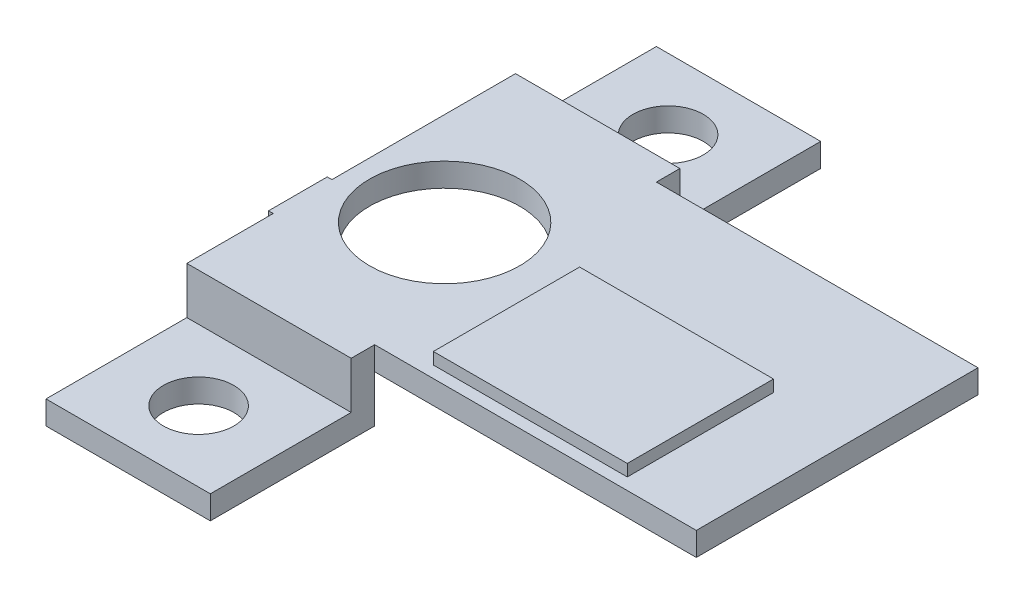
SolidWorks part; units mm, degrees
ref_plane "前视基准面" through (0, 0, 0) normal (0, 0, 1) x (1, 0, 0)
ref_plane "上视基准面" through (0, 0, 0) normal (0, 1, 0) x (1, 0, 0)
ref_plane "右视基准面" through (0, 0, 0) normal (1, 0, 0) x (0, 0, -1)
sketch "草图2" plane through (0, 0, 0) normal (0, 1, 0) x (1, 0, 0)
  line L1 (-8.9775, 5.0216) -> (11.7225, 5.0216)
  line L2 (-8.9775, 5.0216) -> (-8.9775, -6.9784)
  line L3 (-8.9775, -6.9784) -> (11.7225, -6.9784)
  line L4 (11.7225, 5.0216) -> (11.7225, -6.9784)
  line L5 (0.5225, -0.7484) -> (7.7825, -0.7484)
  line L6 (0.5225, -0.7484) -> (0.5225, -5.9784)
  line L7 (0.5225, -5.9784) -> (7.7825, -5.9784)
  line L8 (7.7825, -0.7484) -> (7.7825, -5.9784)
  circle A0 centre (-4.9975, -0.9784) radius 3.2
  dimension "D7" = 6.4
  dimension "D1" = 20.7
  dimension "D2" = 12
  dimension "D3" = 1
  dimension "D4" = 9.5
  dimension "D5" = 5.23
  dimension "D6" = 7.26
  dimension "D8" = 3.98
  dimension "D9" = 6
extrude "凸台-拉伸1" add sketch "草图2" along normal blind 1
sketch "草图3" plane through (0, 1, 0) normal (0, 1, 0) x (1, 0, 0)
  line L0 (7.7825, -5.9784) -> (7.7825, -0.7484) construction
  line L1 (0.0225, -0.2484) -> (8.2825, -0.2484)
  line L2 (0.0225, -0.2484) -> (0.0225, -6.4784)
  line L3 (0.0225, -6.4784) -> (8.2825, -6.4784)
  line L4 (8.2825, -0.2484) -> (8.2825, -6.4784)
  line L5 (7.7825, -0.7484) -> (0.5225, -0.7484) construction
  line L6 (0.5225, -0.7484) -> (0.5225, -5.9784) construction
  line L7 (0.5225, -5.9784) -> (7.7825, -5.9784) construction
  dimension "D1" = 0.5
  dimension "D2" = 0.5
  dimension "D3" = 0.5
  dimension "D4" = 0.5
extrude "凸台-拉伸2" add sketch "草图3" along normal blind 0.5
sketch "草图4" plane through (-8.9775, 0, 0) normal (-1, 0, 0) x (0, 0, 1)
  line L0 (-5.0216, 1) -> (6.9784, 1) construction
  line L1 (1.7984, 1) -> (4.2984, 1)
  line L2 (1.7984, 1) -> (1.7984, 0)
  line L3 (1.7984, 0) -> (4.2984, 0)
  line L4 (4.2984, 1) -> (4.2984, 0)
  line L5 (-5.0216, 0) -> (6.9784, 0) construction
  line L6 (6.9784, 1) -> (6.9784, 0) construction
  point P8 (3.0484, 1)
  point P11 (3.8695, 1)
  dimension "D1" = 3.93
  dimension "D2" = 2.5
extrude "凸台-拉伸3" add sketch "草图4" along normal blind 0.2
sketch "草图5" plane through (0, 0, 6.9784) normal (0, 0, 1) x (1, 0, 0)
  line L1 (-8.9775, 1) -> (-1.9775, 1)
  line L2 (-8.9775, 1) -> (-8.9775, -2)
  line L3 (-8.9775, -2) -> (-1.9775, -2)
  line L4 (-1.9775, 1) -> (-1.9775, -2)
  dimension "D1" = 3
  dimension "D2" = 7
extrude "凸台-拉伸4" add sketch "草图5" along normal blind 1
sketch "草图6" plane through (0, 0, -5.0216) normal (0, 0, -1) x (-1, 0, 0)
  line L1 (8.9775, 1) -> (1.9775, 1)
  line L2 (8.9775, 1) -> (8.9775, -2)
  line L3 (8.9775, -2) -> (1.9775, -2)
  line L4 (1.9775, 1) -> (1.9775, -2)
extrude "凸台-拉伸5" add sketch "草图6" along normal blind 1
sketch "草图7" plane through (0, 0, 7.9784) normal (0, 0, 1) x (1, 0, 0)
  line L0 (-8.9775, 1) -> (-8.9775, -2) construction
  line L1 (-8.9775, -1) -> (-1.9775, -1)
  line L2 (-8.9775, -1) -> (-8.9775, -2)
  line L3 (-8.9775, -2) -> (-1.9775, -2)
  line L4 (-1.9775, -1) -> (-1.9775, -2)
  dimension "D1" = 1
extrude "凸台-拉伸6" add sketch "草图7" along normal blind 6
sketch "草图8" plane through (0, 0, -6.0216) normal (0, 0, -1) x (-1, 0, 0)
  line L0 (8.9775, -2) -> (8.9775, 1) construction
  line L1 (1.9775, -2) -> (8.9775, -2)
  line L2 (1.9775, -2) -> (1.9775, -1)
  line L3 (1.9775, -1) -> (8.9775, -1)
  line L4 (8.9775, -2) -> (8.9775, -1)
  dimension "D1" = 1
extrude "凸台-拉伸7" add sketch "草图8" along normal blind 6
sketch "草图9" plane through (0, -1, 0) normal (0, 1, 0) x (1, 0, 0)
  line L0 (-5.4775, -15.5618) -> (-5.4775, 13.5485) construction
  line L1 (14.038, -0.9784) -> (-11.2022, -0.9784) construction
  line L2 (-8.9775, 12.0216) -> (-1.9775, 12.0216) construction
  circle A0 centre (-5.4775, 9.0216) radius 1.5
  circle A1 centre (-5.4775, -10.9784) radius 1.5
  point P8 (0, 0)
  point P9 (-5.4775, 12.0216)
  dimension "D1" = 3
  dimension "D2" = 3
extrude "切除-拉伸1" cut sketch "草图9" against normal blind 1
